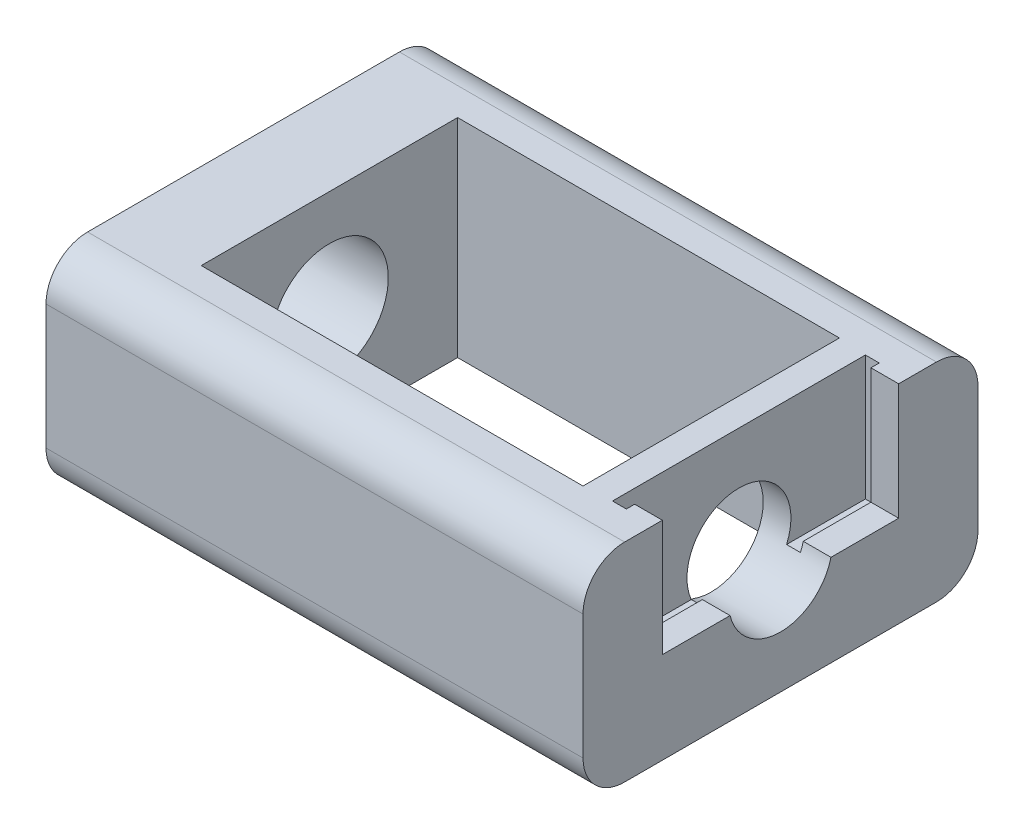
SolidWorks part; units mm, degrees
ref_plane "Front Plane" through (0, 0, 0) normal (0, 0, 1) x (1, 0, 0)
ref_plane "Top Plane" through (0, 0, 0) normal (0, 1, 0) x (1, 0, 0)
ref_plane "Right Plane" through (0, 0, 0) normal (1, 0, 0) x (0, 0, -1)
sketch "Sketch1" plane through (0, 0, 0) normal (1, 0, 0) x (0, 0, -1)
  line L1 (-14.25, -7.5) -> (14.25, -7.5)
  line L2 (-14.25, -7.5) -> (-14.25, 7.5)
  line L3 (-14.25, 7.5) -> (14.25, 7.5)
  line L4 (14.25, -7.5) -> (14.25, 7.5)
  line L5 (-14.25, -7.5) -> (14.25, 7.5) construction
  line L6 (-14.25, 7.5) -> (14.25, -7.5) construction
  circle A0 centre (0, 0) radius 4.25
  point P0 (0, 0)
  dimension "D3" = 8.5
  dimension "D1" = 28.5
  dimension "D2" = 15
extrude "Boss-Extrude1" add sketch "Sketch1" along normal blind 6.2
sketch "Sketch2" plane through (6.2, 0, 0) normal (1, 0, 0) x (0, 0, -1)
  line L0 (14.25, 7.5) -> (-14.25, 7.5) construction
  line L1 (-14.25, 7.5) -> (-9.25, 7.5)
  line L2 (-14.25, 7.5) -> (-14.25, -7.5)
  line L3 (-14.25, -7.5) -> (-9.25, -7.5)
  line L4 (-9.25, 7.5) -> (-9.25, -7.5)
  line L5 (-14.25, 7.5) -> (-9.25, -7.5) construction
  line L6 (-14.25, -7.5) -> (-9.25, 7.5) construction
  line L7 (-14.25, -7.5) -> (14.25, -7.5) construction
  line L8 (0, 0) -> (0, 50000) construction
  line L9 (14.25, -7.5) -> (9.25, -7.5)
  line L10 (9.25, 7.5) -> (9.25, -7.5)
  line L11 (14.25, 7.5) -> (9.25, 7.5)
  line L12 (14.25, 7.5) -> (14.25, -7.5)
  line L13 (-14.25, 7.5) -> (-14.25, -7.5) construction
  point P4 (-11.75, 0)
  point P12 (0, 7.5)
  dimension "D1" = 5
extrude "Boss-Extrude2" add sketch "Sketch2" along normal blind 27.55
sketch "Sketch3" plane through (33.75, 0, 0) normal (1, 0, 0) x (0, 0, -1)
  line L0 (0, 0) -> (0, 50000) construction
  line L1 (14.25, -7.5) -> (-14.25, -7.5)
  line L2 (14.25, -7.5) -> (14.25, 7.5)
  line L3 (14.25, 7.5) -> (-14.25, 7.5)
  line L4 (-14.25, -7.5) -> (-14.25, 7.5)
  line L5 (14.25, -7.5) -> (-14.25, 7.5) construction
  line L6 (14.25, 7.5) -> (-14.25, -7.5) construction
  line L7 (-8.525, 7.5) -> (-8.525, -0.9)
  line L8 (-9.125, -1.5) -> (9.125, -1.5)
  line L9 (-9.125, -1.5) -> (-9.125, 7.5)
  line L10 (-9.125, 7.5) -> (9.125, 7.5)
  line L11 (9.125, -1.5) -> (9.125, 7.5)
  line L12 (-9.125, -1.5) -> (9.125, 7.5) construction
  line L13 (-9.125, 7.5) -> (9.125, -1.5) construction
  line L14 (-8.525, -0.9) -> (8.525, -0.9)
  line L15 (8.525, -0.9) -> (8.525, 7.5)
  circle A0 centre (0, 0) radius 3.75
  point P4 (0, 0)
  point P9 (0, 3)
  line M9 (-14.25, 7.5) -> (-14.25, -7.5)
  line M10 (-14.25, -7.5) -> (-9.25, -7.5)
  line M11 (-9.25, -7.5) -> (-9.25, 7.5)
  line M12 (-9.25, 7.5) -> (-14.25, 7.5)
  dimension "D6" = 7.5
  dimension "D1" = 9
  dimension "D2" = 18.25
  dimension "D3" = 0.6
  dimension "D4" = 0.6
  dimension "D5" = 0.6
extrude "Boss-Extrude3" add sketch "Sketch3" along normal blind 5 contours M12 M9 M10 M11 | A0 L14 L15 L10 L7 | A0 L8 L9 L3 L1 L2 L11 M11 | A0 L14 L7 L3 L9 L8 | A0 L8 L11 L3 L15 L14 region at (33.75, -2.6295, -4.9759) region at (33.75, 0, 11.75) region at (33.75, 3, -9.0185) region at (33.75, 7.3935, 8.825) region at (33.75, 3.8487, 0)
extrude "Cut-Extrude2" cut sketch "Sketch3<6>" along normal blind 1 from offset 2 contours A0 L14 L15 L10 L7 | A0 L14 L7 L3 L9 L8 | A0 L8 L11 L3 L15 L14 region at (33.75, 3, -9.0185) region at (33.75, 7.3935, 8.825) region at (33.75, 3.8487, 0)
sketch "Sketch3<6>" plane through (33.75, 0, 0) normal (1, 0, 0) x (0, 0, -1) same geometry as "Sketch3"
extrude "Cut-Extrude3" cut sketch "Sketch3<7>" along normal through all from surface contours A0 L14 L15 L10 L7 region at (33.75, 3.8487, 0) starting at face at (35.75, 2.375, 0)
sketch "Sketch3<7>" plane through (33.75, 0, 0) normal (1, 0, 0) x (0, 0, -1) same geometry as "Sketch3"
fillet "Fillet1" radius 3 4 edges at (19.375, 7.5, 14.25) (19.375, -7.5, 14.25) (19.375, 7.5, -14.25) (19.375, -7.5, -14.25)
